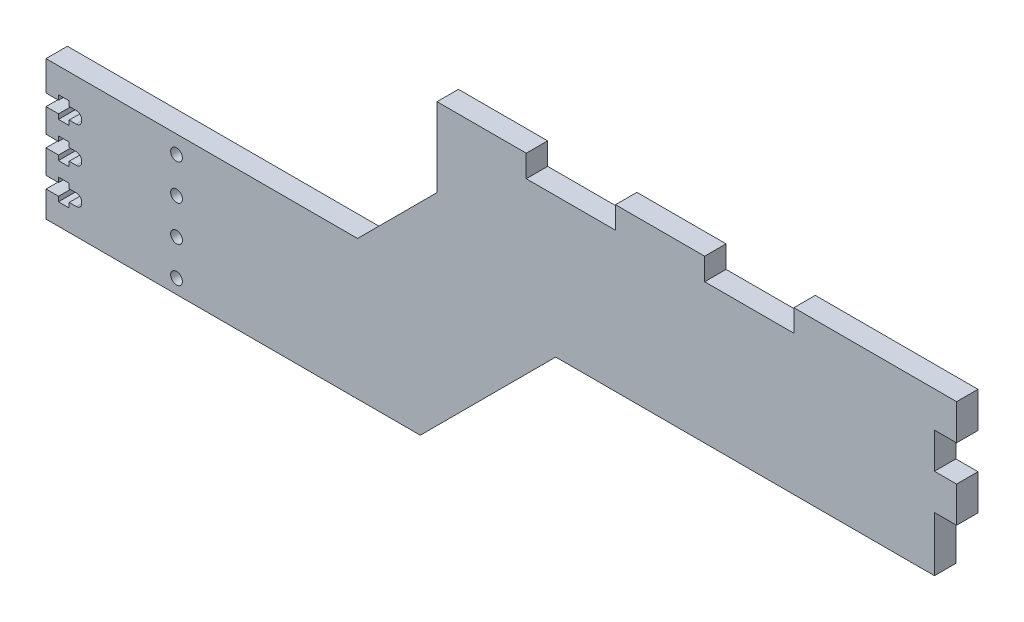
SolidWorks part; units mm, degrees
ref_plane "Спереди" through (0, 0, 0) normal (0, 0, 1) x (1, 0, 0)
ref_plane "Сверху" through (0, 0, 0) normal (0, 1, 0) x (1, 0, 0)
ref_plane "Справа" through (0, 0, 0) normal (1, 0, 0) x (0, 0, -1)
sketch "Эскиз1" plane through (0, 0, 0) normal (0, 0, 1) x (1, 0, 0)
  line L0 (-164.4683, 1.0153) -> (-164.4683, -37.9464)
  line L1 (-54.8861, 45.3538) -> (-54.8861, 23.2989)
  line L2 (-54.8861, 23.2989) -> (-77.1697, 1.0153)
  line L3 (84.5105, 0) -> (-21.6322, 0)
  line L4 (-164.4683, -37.9464) -> (-59.5786, -37.9464)
  line L5 (-77.1697, 1.0153) -> (-164.4683, 1.0153)
  line L7 (90.7105, 35.3538) -> (84.5105, 35.3538)
  line L8 (84.5105, 35.3538) -> (84.5105, 25.3538)
  line L10 (90.7105, 45.3538) -> (45.1139, 45.3538)
  line L11 (-21.6322, 0) -> (-59.5786, -37.9464)
  line L12 (84.5105, 25.3538) -> (90.7105, 25.3538)
  line L13 (90.7105, 25.3538) -> (90.7105, 15.3538)
  line L14 (90.7105, 15.3538) -> (84.5105, 15.3538)
  line L15 (84.5105, 15.3538) -> (84.5105, 0)
  line L16 (90.7105, 35.3538) -> (90.7105, 45.3538)
  line L18 (-29.8861, 45.3538) -> (-29.8861, 39.1538)
  line L19 (-29.8861, 39.1538) -> (-4.8861, 39.1538)
  line L20 (-4.8861, 45.3538) -> (-4.8861, 39.1538)
  line L22 (20.1139, 45.3538) -> (20.1139, 39.1538)
  line L23 (20.1139, 39.1538) -> (45.1139, 39.1538)
  line L24 (45.1139, 39.1538) -> (45.1139, 45.3538)
  line L25 (-29.8861, 45.3538) -> (-54.8861, 45.3538)
  line L26 (20.1139, 45.3538) -> (-4.8861, 45.3538)
  dimension "D1" = 10
  dimension "D8" = 25
  dimension "D2" = 6.2
  dimension "D3" = 10
  dimension "D4" = 10
  dimension "D5" = 25
  dimension "D7" = 25
  dimension "D9" = 25
extrude "Бобышка-Вытянуть1" add sketch "Эскиз1" along normal blind 6
sketch "Эскиз2" plane through (0, 0, 6) normal (0, 0, 1) x (1, 0, 0)
  line L0 (-157.9683, -10.6347) -> (-157.9683, -11.9847)
  line L1 (-160.9683, -5.9847) -> (-157.9683, -5.9847)
  line L2 (-160.9683, -5.9847) -> (-160.9683, -7.3347)
  line L3 (-160.9683, -11.9847) -> (-157.9683, -11.9847)
  line L4 (-157.9683, -5.9847) -> (-157.9683, -7.3347)
  line L5 (-157.9683, -17.3347) -> (-155.9683, -17.3347)
  line L6 (-160.9683, -10.6347) -> (-160.9683, -11.9847)
  line L7 (-160.9683, -15.9847) -> (-157.9683, -15.9847)
  line L8 (-160.9683, -15.9847) -> (-160.9683, -17.3347)
  line L9 (-160.9683, -21.9847) -> (-157.9683, -21.9847)
  line L10 (-157.9683, -15.9847) -> (-157.9683, -17.3347)
  line L11 (-157.9683, -20.6347) -> (-157.9683, -21.9847)
  line L12 (-160.9683, -20.6347) -> (-160.9683, -21.9847)
  line L13 (-160.9683, -25.9847) -> (-157.9683, -25.9847)
  line L14 (-160.9683, -25.9847) -> (-160.9683, -27.3347)
  line L15 (-160.9683, -31.9847) -> (-157.9683, -31.9847)
  line L16 (-157.9683, -25.9847) -> (-157.9683, -27.3347)
  line L17 (-157.9683, -30.6347) -> (-155.9683, -30.6347)
  line L19 (-164.4683, -17.3347) -> (-160.9683, -17.3347)
  line L20 (-164.4683, -17.3347) -> (-164.4683, -20.6347)
  line L21 (-164.4683, -20.6347) -> (-160.9683, -20.6347)
  line L22 (-154.4683, -18.8347) -> (-154.4683, -19.1347)
  line L23 (-164.4683, -7.3347) -> (-160.9683, -7.3347)
  line L24 (-164.4683, -7.3347) -> (-164.4683, -10.6347)
  line L25 (-164.4683, -10.6347) -> (-160.9683, -10.6347)
  line L26 (-154.4683, -8.8347) -> (-154.4683, -9.1347)
  line L27 (-157.9683, -20.6347) -> (-155.9683, -20.6347)
  line L28 (-157.9683, -30.6347) -> (-157.9683, -31.9847)
  line L29 (-157.9683, -10.6347) -> (-155.9683, -10.6347)
  line L30 (-157.9683, -7.3347) -> (-155.9683, -7.3347)
  line L31 (-164.4683, -27.3347) -> (-160.9683, -27.3347)
  line L32 (-164.4683, -27.3347) -> (-164.4683, -30.6347)
  line L33 (-164.4683, -30.6347) -> (-160.9683, -30.6347)
  line L34 (-154.4683, -28.8347) -> (-154.4683, -29.1347)
  line L37 (-160.9683, -30.6347) -> (-160.9683, -31.9847)
  line L38 (-157.9683, -27.3347) -> (-155.9683, -27.3347)
  circle A0 centre (-127.8883, -3.9847) radius 1.65
  arc A1 (-154.4683, -29.1347) -> (-155.9683, -30.6347) centre (-155.9683, -29.1347) cw
  circle A2 centre (-127.8883, -13.9847) radius 1.65
  arc A3 (-154.4683, -28.8347) -> (-155.9683, -27.3347) centre (-155.9683, -28.8347) ccw
  circle A4 centre (-127.8883, -23.9847) radius 1.65
  arc A5 (-154.4683, -8.8347) -> (-155.9683, -7.3347) centre (-155.9683, -8.8347) ccw
  circle A6 centre (-127.8883, -33.9847) radius 1.65
  arc A7 (-154.4683, -9.1347) -> (-155.9683, -10.6347) centre (-155.9683, -9.1347) cw
  arc A8 (-154.4683, -18.8347) -> (-155.9683, -17.3347) centre (-155.9683, -18.8347) ccw
  arc A9 (-154.4683, -19.1347) -> (-155.9683, -20.6347) centre (-155.9683, -19.1347) cw
  point P0 (-159.4683, -8.9847)
  point P5 (-159.4683, -18.9847)
  point P11 (-159.4683, -18.9847)
  point P18 (-159.4683, -28.9847)
  point P32 (-159.4683, -28.9847)
  point P35 (-159.4683, -8.9847)
  dimension "D5" = 3.3
  dimension "D6" = 3
  dimension "D7" = 6
  dimension "D8" = 3
  dimension "D13" = 3.3
  dimension "D15" = 3.3
  dimension "D9" = 1.5
  dimension "D10" = 1.5
  dimension "D2" = 6
  dimension "D3" = 3
  dimension "D4" = 6
extrude "Вырез-Вытянуть1" cut sketch "Эскиз2" against normal through all
